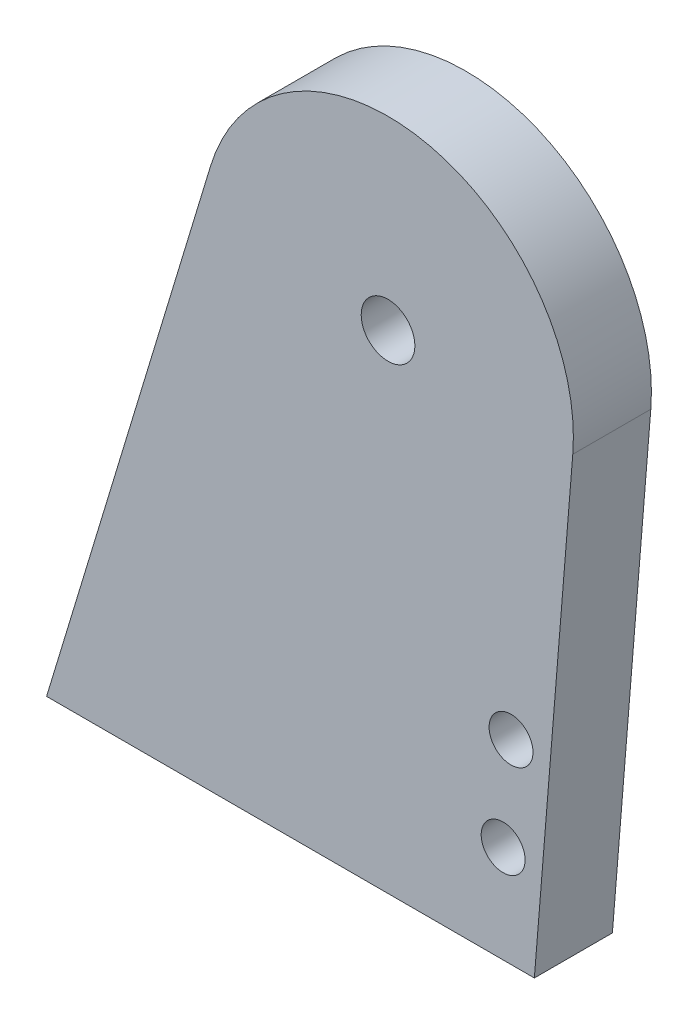
SolidWorks part; units mm, degrees
material "5052-O"
ref_plane "정면" through (0, 0, 0) normal (0, 0, 1) x (1, 0, 0)
ref_plane "윗면" through (0, 0, 0) normal (0, 1, 0) x (1, 0, 0)
ref_plane "우측면" through (0, 0, 0) normal (1, 0, 0) x (0, 0, -1)
sketch "스케치1" plane through (0, 0, 0) normal (0, 0, 1) x (1, 0, 0)
  line L0 (0, 0) -> (50, 0)
  line L1 (50, 0) -> (53.9376, 48.4613)
  line L2 (0, 0) -> (16.8161, 55.5087)
  circle A0 centre (35, 50) radius 19
  dimension "D1" = 38
  dimension "D2" = 50
  dimension "D3" = 50
  dimension "D5" = 15
extrude "보스-돌출1" add sketch "스케치1" along normal blind 8 contours A0 L2 L0 L1 | A0 region at (27.7427, 17.8369, 0) region at (35, 50, 0)
hole_wizard "M4 여유 구멍1" positions "스케치2" profile "스케치3" hole size "M4" standard "ISO" end condition up to next
sketch "스케치2" plane through (0, 0, 8) normal (0, 0, 1) x (1, 0, 0)
  line L0 (47.6092, 19.9672) -> (46.7993, 10)
  line L2 (50, 0) -> (53.9376, 48.4613) construction
  line L3 (0, 0) -> (50, 0) construction
  point P0 (46.7993, 10)
  point P2 (47.6092, 19.9672)
  dimension "D1" = 10
  dimension "D2" = 4
  dimension "D3" = 10
sketch "스케치3" plane through (46.7993, 10, 8) normal (1, 0, 0) x (0, -1, 0)
  line L0 (0, 0) -> (0, 8)
  line L1 (0, 8) -> (2.25, 8)
  line L2 (2.25, 8) -> (2.25, 0)
  line L5 (2.25, 0) -> (0, 0)
  line L11 (0, -6.35) -> (0, 107.95) construction
  dimension "관통 구멍 지름" = 4.5
  dimension "관통 구멍 깊이" = 8
hole_wizard "M3 나사 구멍1" positions "스케치4" profile "스케치5" tap size "M3" standard "ISO"
sketch "스케치4" plane through (0, 0, 0) normal (0, -1, 0) x (-1, 0, 0)
  line L0 (-10, -4) -> (-40, -4)
  line L2 (0, 0) -> (-50, 0) construction
  line L3 (-50, -8) -> (-50, 0) construction
  point P0 (-10, -4)
  point P2 (-40, -4)
  point P8 (-25, -4)
  point P11 (-25, 0)
  point P14 (-50, -4)
  dimension "D1" = 30
sketch "스케치5" plane through (10, 0, 4) normal (1, 0, 0) x (0, 0, -1)
  line L0 (0, 0) -> (0, 9.2511)
  line L1 (0, 9.2511) -> (1.25, 8.5)
  line L2 (1.25, 8.5) -> (1.25, 0.275)
  line L3 (1.25, 0.275) -> (1.525, 0)
  line L5 (1.525, 0) -> (0, 0)
  line L6 (-1.25, 0.275) -> (-1.525, 0) construction
  line L10 (0, 9.2511) -> (-1.25, 8.5) construction
  line L11 (0, -6.35) -> (0, 107.95) construction
  dimension "탭 드릴 지름" = 2.5
  dimension "탭 드릴 깊이" = 8.5
  dimension "표면 카운터싱크 지름" = 3.05
  dimension "표면 카운터싱크 각도" = 90
  dimension "드릴 각도" = 118
cosmetic thread "구멍 나사산1" parameters "D1"=6, "D2"=3
cosmetic thread "구멍 나사산2" parameters "D1"=6, "D2"=3
hole_wizard "M5 여유 구멍1" positions "스케치6" profile "스케치7" hole size "M5" standard "ISO" end condition through all
sketch "스케치6" plane through (0, 0, 0) normal (0, 0, -1) x (-1, 0, 0)
  point P0 (-35, 50)
sketch "스케치7" plane through (35, 50, 0) normal (1, 0, 0) x (0, 1, 0)
  line L0 (0, 0) -> (0, 8)
  line L1 (0, 8) -> (2.75, 8)
  line L2 (2.75, 8) -> (2.75, 0)
  line L5 (2.75, 0) -> (0, 0)
  line L11 (0, -6.35) -> (0, 107.95) construction
  dimension "관통 구멍 지름" = 5.5
  dimension "관통 구멍 깊이" = 8
